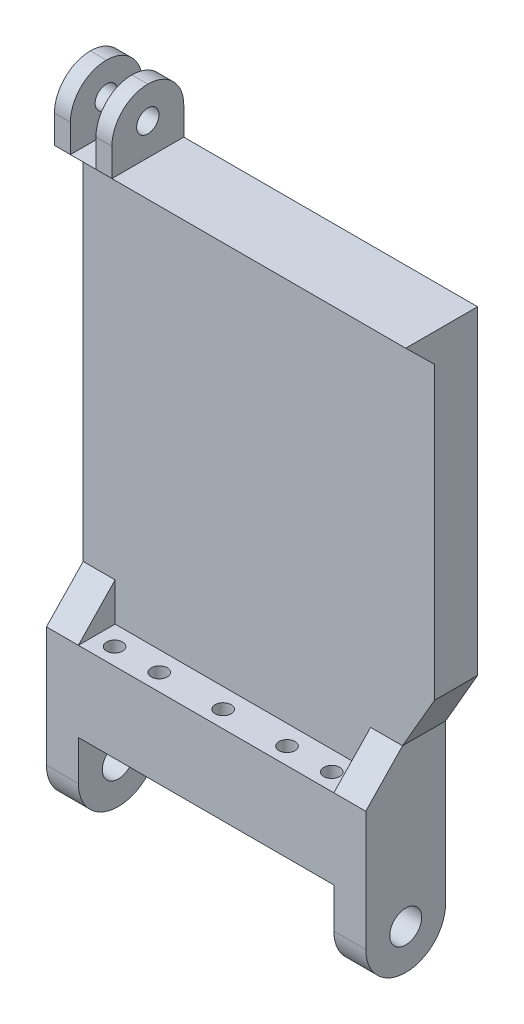
SolidWorks part; units mm, degrees
ref_plane "Front Plane" through (0, 0, 0) normal (0, 0, 1) x (1, 0, 0)
ref_plane "Top Plane" through (0, 0, 0) normal (0, 1, 0) x (1, 0, 0)
ref_plane "Right Plane" through (0, 0, 0) normal (1, 0, 0) x (0, 0, -1)
sketch "Sketch1" plane through (0, 0, 0) normal (0, 0, 1) x (1, 0, 0)
  line L1 (0, 0) -> (50, 0)
  line L2 (0, 0) -> (0, -12.5)
  line L3 (0, -12.5) -> (50, -12.5)
  line L4 (50, 0) -> (50, -12.5)
  line L5 (0, -12.5) -> (5, -12.5)
  line L6 (0, -12.5) -> (0, -25)
  line L7 (0, -25) -> (5, -25)
  line L8 (5, -12.5) -> (5, -25)
  line L9 (50, -12.5) -> (45, -12.5)
  line L10 (50, -12.5) -> (50, -25)
  line L11 (50, -25) -> (45, -25)
  line L12 (45, -12.5) -> (45, -25)
  dimension "D1" = 50
  dimension "D2" = 12.5
  dimension "D3" = 5
  dimension "D4" = 5
  dimension "D5" = 12.5
  dimension "D6" = 12.5
extrude "Boss-Extrude1" add sketch "Sketch1" along normal blind 12.5 contours L4 L1 L2 L3 | L8 L3 L6 L7 | L3 L12 L11 L10 region at (25, -6.25, 0) region at (2.5, -18.75, 0) region at (47.5, -18.75, 0)
fillet "Fillet1" radius 6.25 4 edges at (2.5, -25, 12.5) (2.5, -25, 0) (47.5, -25, 12.5) (47.5, -25, 0)
sketch "Sketch2" plane through (5, 0, 0) normal (1, 0, 0) x (0, 0, -1)
  line L0 (-6.25, -25) -> (-6.25, -12.5) construction
  line L1 (-12.5, -12.5) -> (0, -12.5) construction
  circle A0 centre (-6.25, -18.75) radius 2.5
  dimension "D1" = 5
extrude "Cut-Extrude1" cut sketch "Sketch2" against normal blind 24.5 and the other way blind 77.5
sketch "Sketch4" plane through (0, -12.5, 0) normal (0, -1, 0) x (-1, 0, 0)
  line L0 (-8, -9.8356) -> (-5, -9.8356) construction
  line L1 (-5, -12.5) -> (-5, 0) construction
  line L2 (-45, -9.8356) -> (-5, -9.8356) construction
  line L3 (-5, -9.8356) -> (-8, -9.8356) construction
  line L4 (-8, -9.8356) -> (-45, -9.8356) construction
  line L5 (-45, -12.5) -> (-45, 0) construction
  line L22 (-5, -6.25) -> (-5, -12.5) construction
  circle A0 centre (-8, -9.8356) radius 1.25
  circle A1 centre (-15, -9.8356) radius 1.25
  circle A2 centre (-25, -9.8356) radius 1.25
  circle A3 centre (-35, -9.8356) radius 1.25
  circle A4 centre (-42, -9.8356) radius 1.25
  dimension "D1" = 2.5
  dimension "D2" = 2.5
  dimension "D3" = 2.5
  dimension "D4" = 2.5
  dimension "D5" = 2.5
  dimension "D6" = 3
  dimension "D7" = 3
  dimension "D8" = 7
  dimension "D9" = 7
  dimension "D10" = 20
extrude "Cut-Extrude2" cut sketch "Sketch4" against normal blind 12.5
sketch "Sketch5" plane through (0, 0, 0) normal (0, 1, 0) x (1, 0, 0)
  line L0 (50, -12.5) -> (50, 0) construction
  line L1 (0, 0) -> (50, 0)
  line L2 (0, 0) -> (0, -6.75)
  line L3 (0, -6.75) -> (50, -6.75)
  line L4 (50, 0) -> (50, -6.75)
  line L5 (0, -12.5) -> (5.75, -6.75)
  line L6 (5.75, -6.75) -> (0, -6.75)
  line L7 (50, -12.5) -> (44.25, -6.75)
  line L8 (44.25, -6.75) -> (50, -6.75)
  line L9 (2.875, -9.625) -> (2.875, -12.5)
  line L10 (0, -12.5) -> (50, -12.5) construction
  line L11 (2.875, -12.5) -> (0, -12.5)
  line L12 (47.125, -9.625) -> (47.125, -12.5)
  line L13 (47.125, -12.5) -> (50, -12.5)
  line M6 (50, 0) -> (0, 0)
  line M7 (0, 0) -> (0, -12.5)
  line M9 (50, -12.5) -> (50, 0)
  dimension "D1" = 6.75
extrude "Boss-Extrude4" add sketch "Sketch5" along normal blind 6 contours L3 M7 M9 M6 region at (25, 0, 3.375)
sketch "Sketch6" plane through (0, 0, 0) normal (-1, 0, 0) x (0, 0, 1)
  line L0 (6.75, 6) -> (12.5, 0)
  line L1 (12.5, 0) -> (6.75, 0)
  line L2 (6.75, 0) -> (6.75, 6)
extrude "Boss-Extrude5" add sketch "Sketch6" against normal blind 5
sketch "Sketch7" plane through (50, 0, 0) normal (1, 0, 0) x (0, 0, -1)
  line L0 (-6.75, 6) -> (-12.5, 0)
  line L1 (-12.5, 0) -> (-6.75, 0)
  line L2 (-6.75, 0) -> (-6.75, 6)
extrude "Boss-Extrude6" add sketch "Sketch7" against normal blind 5
sketch "Sketch8" plane through (0, 0, 0) normal (0, 0, -1) x (-1, 0, 0)
  line L0 (-50, 6) -> (-55, 14.6603)
  line L1 (-55, 14.6603) -> (-55, 64.6603)
  line L2 (-55, 64.6603) -> (0, 64.6603)
  line L3 (0, 64.6603) -> (0, 6)
  line L4 (0, 6) -> (-50, 6)
  dimension "D1" = 10
  dimension "D2" = 50
  dimension "D3" = 55
extrude "Boss-Extrude8" add sketch "Sketch8" against normal blind 6.75
sketch "Sketch10" plane through (0, 0, 0) normal (-1, 0, 0) x (0, 0, 1)
  line L0 (6.75, 64.6603) -> (11.25, 64.6603)
  line L1 (11.25, 64.6603) -> (6.75, 60.2257)
  line L2 (6.75, 6) -> (6.75, 64.6603) construction
  line L3 (6.75, 64.6603) -> (6.75, 60.2257)
  dimension "D1" = 4.5
extrude "Boss-Extrude10" add sketch "Sketch10" against normal blind 55
sketch "Sketch12" plane through (0, 0, 0) normal (0, 0, -1) x (-1, 0, 0)
  line L0 (0, 64.6603) -> (0, 74.6603)
  line L1 (0, 74.6603) -> (-2.5, 74.6603)
  line L2 (-2.5, 74.6603) -> (-2.5, 64.6603)
  line L3 (0, 64.6603) -> (-55, 64.6603) construction
  line L4 (-2.5, 64.6603) -> (0, 64.6603)
  dimension "D1" = 10
  dimension "D2" = 2.5
extrude "Boss-Extrude11" add sketch "Sketch12" against normal blind 11.25
sketch "Sketch14" plane through (0, 0, 0) normal (0, 0, -1) x (-1, 0, 0)
  line L0 (-55, 64.6603) -> (-2.5, 64.6603) construction
  line L1 (-6.5, 64.6603) -> (-9, 64.6603)
  line L2 (-6.5, 64.6603) -> (-6.5, 74.6603)
  line L3 (-6.5, 74.6603) -> (-9, 74.6603)
  line L4 (-9, 64.6603) -> (-9, 74.6603)
  line L5 (-2.5, 74.6603) -> (-2.5, 64.6603) construction
  dimension "D1" = 2.5
  dimension "D2" = 4
extrude "Boss-Extrude12" add sketch "Sketch14" against normal blind 11.25
fillet "Fillet2" radius 5.625 4 edges at (7.75, 74.6603, 0) (1.25, 74.6603, 11.25) (1.25, 74.6603, 0) (7.75, 74.6603, 11.25)
sketch "Sketch16" plane through (9, 0, 0) normal (1, 0, 0) x (0, 0, -1)
  line L0 (-5.625, 74.6603) -> (-5.625, 64.6603) construction
  line L1 (-11.25, 64.6603) -> (0, 64.6603) construction
  circle A0 centre (-5.625, 69.6603) radius 1.75
  dimension "D1" = 3.5
extrude "Cut-Extrude3" cut sketch "Sketch16" against normal blind 18.25
